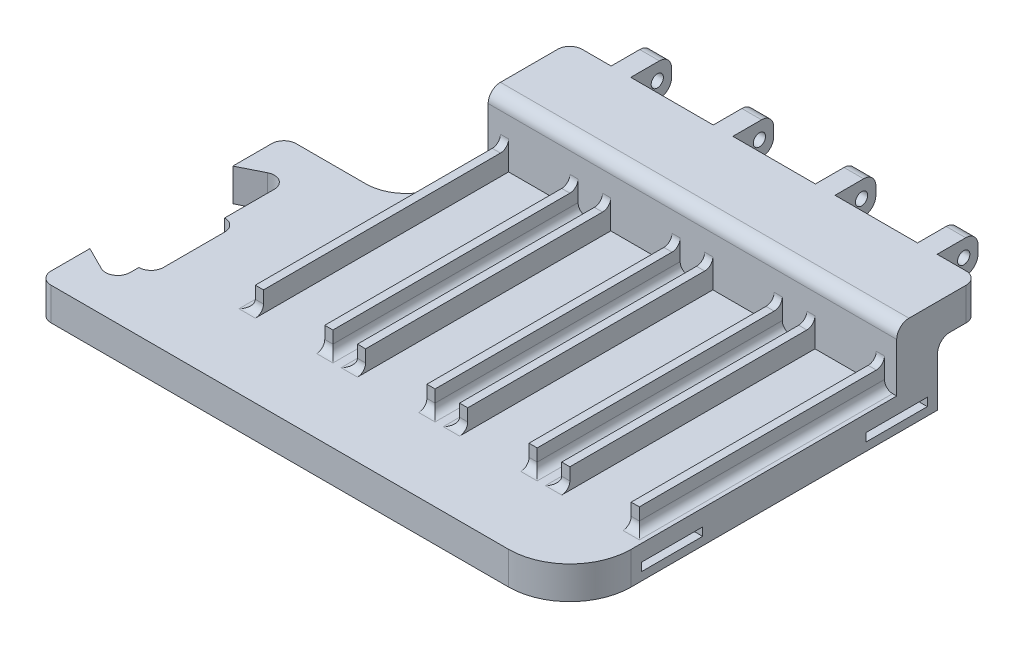
SolidWorks part; units mm, degrees
ref_plane "Alzado" through (0, 0, 0) normal (0, 0, 1) x (1, 0, 0)
ref_plane "Planta" through (0, 0, 0) normal (0, 1, 0) x (1, 0, 0)
ref_plane "Vista lateral" through (0, 0, 0) normal (1, 0, 0) x (0, 0, -1)
sketch "Croquis1" plane through (0, 0, 0) normal (1, 0, 0) x (0, 0, -1)
  line L0 (0, 11.5) -> (0, 3.5) construction
  line L9 (-1.5, 11.5) -> (-111.5, 11.5) construction
  line L18 (0, 11.5) -> (0, -11.5) construction
  line L19 (0, -11.5) -> (-111.5, -11.5) construction
  line L25 (0, 3.5) -> (-21.5, 3.5) construction
  line L26 (0, 3.5) -> (0, -2.6179) construction
  line L29 (0, -2.6179) -> (0, -11.5) construction
  line L31 (-1.5, 11.5) -> (-1.5, 3.5)
  line L32 (-21.5, 3.5) -> (-1.5, 3.5)
  line L35 (-111.5, -11.5) -> (-21.5, -11.5)
  line L56 (-111.5, 11.5) -> (-111.5, -11.5)
  line L59 (0, 11.5) -> (-111.5, 11.5) construction
  line L61 (-21.5, 3.5) -> (-21.5, -11.5)
  line L65 (-1.5, 11.5) -> (-111.5, 11.5)
  circle A0 centre (-5, 7.5) radius 1.5
  point P9 (0, 0)
  point P12 (0, 7.5)
  dimension "D6" = 3
  dimension "D1" = 20
  dimension "D2" = 15
  dimension "D3" = 90
  dimension "D4" = 8
  dimension "D7" = 5
  dimension "D8" = 3
extrude "Saliente-Extruir1" add sketch "Croquis1" along normal mid plane 100
sketch "Croquis2" plane through (0, 0, 0) normal (0, 1, 0) x (1, 0, 0)
  line L17 (50, -1.5) -> (-50, -1.5) construction
  line L18 (-39.9, -1.5) -> (-35.1, -1.5) construction
  line L19 (-39.9, -1.5) -> (-39.9, -11.5)
  line L20 (-39.9, -11.5) -> (-35.1, -11.5) construction
  line L21 (-35.1, -1.5) -> (-35.1, -11.5)
  line L23 (-14.9, -1.5) -> (-10.1, -1.5) construction
  line L24 (-14.9, -1.5) -> (-14.9, -11.5)
  line L25 (-14.9, -11.5) -> (-10.1, -11.5) construction
  line L26 (-10.1, -1.5) -> (-10.1, -11.5)
  line L27 (10.1, -1.5) -> (14.9, -1.5) construction
  line L28 (10.1, -1.5) -> (10.1, -11.5)
  line L29 (10.1, -11.5) -> (14.9, -11.5) construction
  line L30 (14.9, -1.5) -> (14.9, -11.5)
  line L31 (35.1, -1.5) -> (39.9, -1.5) construction
  line L32 (35.1, -1.5) -> (35.1, -11.5)
  line L33 (35.1, -11.5) -> (39.9, -11.5) construction
  line L34 (39.9, -1.5) -> (39.9, -11.5)
  line L39 (-39.9, -6.5) -> (39.9, -6.5) construction
  line L40 (14.9, -1.5) -> (35.1, -1.5)
  line L41 (14.9, -11.5) -> (35.1, -11.5)
  line L42 (-10.1, -1.5) -> (10.1, -1.5)
  line L43 (-10.1, -11.5) -> (10.1, -11.5)
  line L44 (-35.1, -11.5) -> (-14.9, -11.5)
  line L45 (-35.1, -1.5) -> (-14.9, -1.5)
  line L46 (-39.9, -1.5) -> (-50, -1.5)
  line L47 (-50, -1.5) -> (-50, -11.5)
  line L48 (-50, -11.5) -> (-39.9, -11.5)
  line L49 (39.9, -1.5) -> (50, -1.5)
  line L50 (50, -1.5) -> (50, -11.5)
  line L51 (50, -11.5) -> (39.9, -11.5)
  point P23 (-37.5, -11.5)
  point P24 (-12.5, -11.5)
  point P25 (12.5, -11.5)
  point P26 (37.5, -11.5)
  point P29 (0, -6.5)
  dimension "D1" = 4.8
  dimension "D2" = 25
  dimension "D3" = 25
  dimension "D4" = 25
  dimension "D5" = 10
extrude "Cortar-Extruir1" cut sketch "Croquis2" against normal through all both and the other way through all
fillet "Redondeo3" radius 3 11 edges at (-37.5, 11.5, 1.5) (-37.5, 3.5, 1.5) (37.5, 11.5, 1.5) (37.5, 3.5, 1.5) (12.5, 11.5, 1.5) (12.5, 3.5, 1.5) (-12.5, 11.5, 1.5) (-12.5, 3.5, 1.5) (0, 3.5, 21.5) (50, 7.5, 11.5) (-50, 7.5, 11.5)
sketch "Croquis6" plane through (-50, 0, 0) normal (-1, 0, 0) x (0, 0, 1)
  line L1 (31.5, 11.5) -> (111.5, 11.5)
  line L2 (31.5, 11.5) -> (31.5, -3.5)
  line L3 (31.5, -3.5) -> (111.5, -3.5)
  line L4 (111.5, 11.5) -> (111.5, -3.5)
  line L5 (111.5, 11.5) -> (111.5, -11.5) construction
  line L6 (21.5, -11.5) -> (21.5, 0.5) construction
  line L7 (14.5, 11.5) -> (111.5, 11.5) construction
  dimension "D1" = 15
  dimension "D2" = 10
extrude "Cortar-Extruir5" cut sketch "Croquis6" against normal through all contours L2 L3 L4 L1
sketch "Croquis29" plane through (0, -3.5, 0) normal (0, 1, 0) x (1, 0, 0)
  line L0 (50, -31.5) -> (-50, -31.5) construction
  line L2 (-45, -91.5) -> (-45, -31.5)
  line L3 (-45, -31.5) -> (-47, -31.5)
  line L4 (-47, -91.5) -> (-47, -31.5)
  line L6 (-28, -91.5) -> (-28, -31.5)
  line L7 (-28, -31.5) -> (-30, -31.5)
  line L8 (-30, -91.5) -> (-30, -31.5)
  line L9 (-45, -91.5) -> (-47, -91.5)
  line L10 (-39.9, -11.5) -> (-39.9, -4.5) construction
  line L11 (-22, -91.5) -> (-22, -31.5)
  line L12 (-45, -91.5) -> (-30, -91.5) construction
  line L16 (-20, -31.5) -> (-22, -31.5)
  line L17 (-20, -91.5) -> (-20, -31.5)
  line L18 (-20, -91.5) -> (-5, -91.5) construction
  line L19 (-5, -91.5) -> (-5, -31.5)
  line L20 (-3, -31.5) -> (-5, -31.5)
  line L21 (-3, -91.5) -> (-3, -31.5)
  line L23 (3, -91.5) -> (3, -31.5)
  line L24 (5, -31.5) -> (3, -31.5)
  line L25 (5, -91.5) -> (5, -31.5)
  line L26 (5, -91.5) -> (20, -91.5) construction
  line L27 (20, -91.5) -> (20, -31.5)
  line L28 (22, -31.5) -> (20, -31.5)
  line L29 (22, -91.5) -> (22, -31.5)
  line L31 (28, -91.5) -> (28, -31.5)
  line L32 (30, -31.5) -> (28, -31.5)
  line L33 (30, -91.5) -> (30, -31.5)
  line L34 (30, -91.5) -> (45, -91.5) construction
  line L35 (45, -91.5) -> (45, -31.5)
  line L36 (47, -31.5) -> (45, -31.5)
  line L37 (47, -91.5) -> (47, -31.5)
  line L39 (-14.9, -11.5) -> (-14.9, -4.5) construction
  line L40 (-30, -91.5) -> (-28, -91.5)
  line L41 (-20, -91.5) -> (-22, -91.5)
  line L42 (-5, -91.5) -> (-3, -91.5)
  line L43 (5, -91.5) -> (3, -91.5)
  line L44 (20, -91.5) -> (22, -91.5)
  line L45 (30, -91.5) -> (28, -91.5)
  line L46 (45, -91.5) -> (47, -91.5)
  dimension "D1" = 15
  dimension "D2" = 2
  dimension "D3" = 60
  dimension "D4" = 9.9
  dimension "D7" = 9.9
  dimension "D6" = 4
extrude "Saliente-Extruir16" add sketch "Croquis29" along normal blind 5
fillet "Redondeo17" radius 2 24 edges at (-22, -3.5, 61.5) (3, -3.5, 61.5) (28, -3.5, 61.5) (47, -3.5, 61.5) (46, -3.5, 91.5) (29, -3.5, 91.5) (22, -3.5, 61.5) (21, -3.5, 91.5) (4, -3.5, 91.5) (-4, -3.5, 91.5) (-3, -3.5, 61.5) (-21, -3.5, 91.5) (-29, -3.5, 91.5) (-28, -3.5, 61.5) (-46, -3.5, 91.5) (-47, -3.5, 61.5) (-4, 1.5, 31.5) (21, 1.5, 31.5) (46, 1.5, 31.5) (29, 1.5, 31.5) (4, 1.5, 31.5) (-21, 1.5, 31.5) (-29, 1.5, 31.5) (-46, 1.5, 31.5)
sketch "Croquis19" plane through (-50, 0, 0) normal (-1, 0, 0) x (0, 0, 1)
  line L0 (31.5, -3.5) -> (111.5, -3.5) construction
  line L1 (51.5, -3.5) -> (111.5, -3.5)
  line L2 (51.5, -3.5) -> (51.5, -11.5)
  line L3 (51.5, -11.5) -> (111.5, -11.5)
  line L4 (111.5, -3.5) -> (111.5, -11.5)
  line L5 (111.5, -11.5) -> (21.5, -11.5) construction
  line L6 (111.5, -3.5) -> (111.5, -11.5) construction
  dimension "D1" = 60
extrude "Saliente-Extruir10" add sketch "Croquis19" along normal blind 30 contours L2 L3 L4 L1
fillet "Redondeo12" radius 15 1 edges at (50, -7.5, 111.5)
fillet "Redondeo15" radius 3 1 edges at (0, 11.5, 31.5)
fillet "Redondeo23" radius 10 1 edges at (-50, -7.5, 51.5)
sketch "Croquis30" plane through (0, -3.5, 0) normal (0, 1, 0) x (1, 0, 0)
  line L0 (-80, -64) -> (-74.3416, -61.1708)
  line L1 (-80, -51.5) -> (-80, -111.5) construction
  line L2 (-70, -63.8541) -> (-70, -99.1459)
  line L3 (-74.3416, -101.8292) -> (-80, -99)
  line L4 (-80, -99) -> (-80, -64)
  arc A0 (-70, -99.1459) -> (-74.3416, -101.8292) centre (-73, -99.1459) cw
  arc A1 (-74.3416, -61.1708) -> (-70, -63.8541) centre (-73, -63.8541) cw
  point P4 (-70, -81.5)
  point P7 (-80, -81.5)
  point P9 (-80, -81.5)
  point P12 (-70, -104)
  point P15 (-70, -59)
  dimension "D4" = 3
  dimension "D1" = 10
  dimension "D2" = 5
  dimension "D3" = 45
extrude "Cortar-Extruir6" cut sketch "Croquis30" against normal through all
sketch "Croquis4" plane through (0, 0, 0) normal (1, 0, 0) x (0, 0, -1)
  line L0 (-94, -7.5) -> (-79, -7.5)
  line L5 (-96.5, -11.5) -> (-21.5, -11.5) construction
  line L6 (-94, -7.5) -> (-94, -9.5)
  line L7 (-21.5, -11.5) -> (-21.5, 0.5) construction
  line L8 (-39, -7.5) -> (-24, -7.5)
  line L9 (-39, -7.5) -> (-39, -9.5)
  line L10 (-39, -9.5) -> (-24, -9.5)
  line L11 (-24, -7.5) -> (-24, -9.5)
  line L12 (-94, -9.5) -> (-79, -9.5)
  line L13 (-79, -7.5) -> (-79, -9.5)
  line L14 (-96.5, -11.5) -> (-21.5, -11.5) construction
  point P7 (-31.5, -9.5)
  dimension "D1" = 2
  dimension "D2" = 2
  dimension "D3" = 15
  dimension "D4" = 10
  dimension "D5" = 2
  dimension "D6" = 15
  dimension "D7" = 2
  dimension "D8" = 40
extrude "Cortar-Extruir4" cut sketch "Croquis4" against normal through all both and the other way through all
fillet "Redondeo24" radius 3 2 edges at (-80, -7.5, 51.5) (-80, -7.5, 111.5)
sketch "Croquis31" plane through (0, -3.5, 0) normal (0, 1, 0) x (1, 0, 0)
  line L1 (-70, -76) -> (-67, -76)
  line L2 (-70, -76) -> (-70, -97)
  line L3 (-70, -97) -> (-67, -97)
  line L4 (-67, -76) -> (-67, -97)
  line L5 (-70, -79) -> (50, -79) construction
  line L6 (-70, -94) -> (50, -94) construction
  line L7 (-70, -99.1459) -> (-70, -63.8541) construction
  point P7 (0, 0)
  point P8 (0, 0)
  point P9 (0, 0)
  dimension "D1" = 3
  dimension "D2" = 3
  dimension "D3" = 3
extrude "Cortar-Extruir7" cut sketch "Croquis31" against normal through all
fillet "Redondeo27" radius 3 2 edges at (-67, -7.5, 76) (-67, -7.5, 97)
